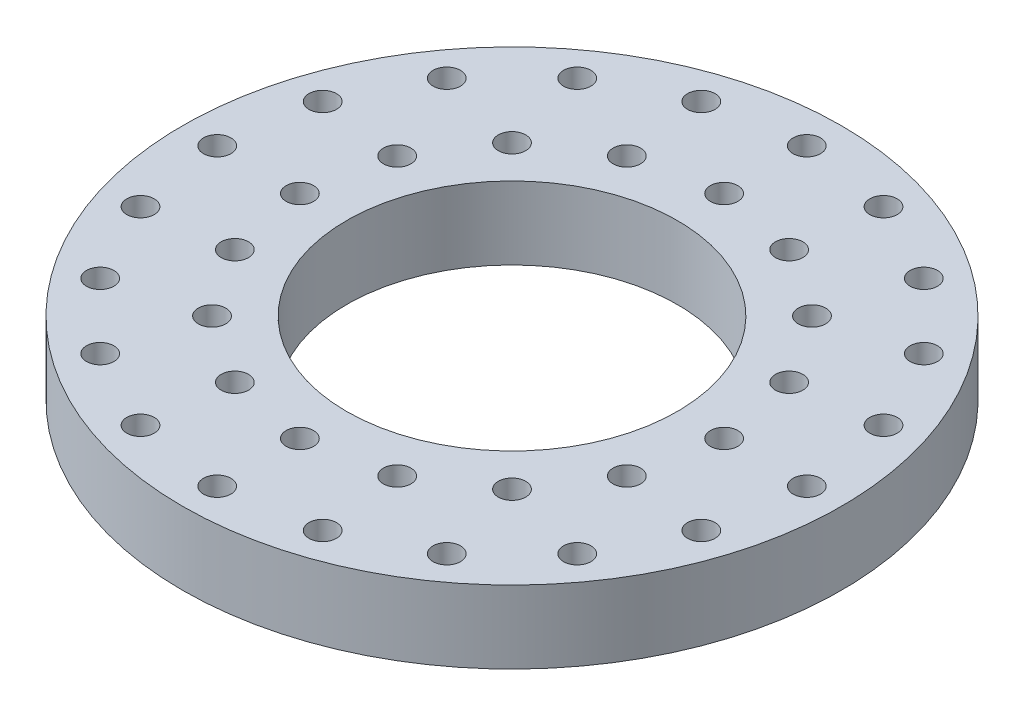
SolidWorks part; units mm, degrees
ref_plane "Front Plane" through (0, 0, 0) normal (0, 0, 1) x (1, 0, 0)
ref_plane "Top Plane" through (0, 0, 0) normal (0, 1, 0) x (1, 0, 0)
ref_plane "Right Plane" through (0, 0, 0) normal (1, 0, 0) x (0, 0, -1)
sketch "Sketch1" plane through (0, 0, 0) normal (0, 1, 0) x (1, 0, 0)
  circle A0 centre (0, 0) radius 101.219
  dimension "D1" = 202.438
extrude "Extrude1" add sketch "Sketch1" along normal blind 22.352
sketch "Sketch2" plane through (0, 0, 0) normal (0, 1, 0) x (1, 0, 0)
  circle A0 centre (0, 0) radius 50.8
extrude "Cut-Extrude1" cut sketch "Sketch2" along normal blind 22.352
sketch "Sketch3" plane through (0, 0, 0) normal (0, 1, 0) x (1, 0, 0)
  circle A0 centre (0, 65.151) radius 4.2164
extrude "Cut-Extrude3" cut sketch "Sketch3" along normal blind 22.352
ref_axis "Axis1" through (0, 103.9235, 0) along (0, -1, 0)
pattern_circular "CirPattern1" count 16 over 360 about axis through (0, 103.9235, 0) along (0, -1, 0) of "Cut-Extrude3"
sketch "Sketch4" plane through (0, 0, 0) normal (0, 1, 0) x (1, 0, 0)
  circle A0 centre (0, 90.551) radius 4.2164
extrude "Cut-Extrude4" cut sketch "Sketch4" along normal blind 22.352
pattern_circular "CirPattern2" count 20 over 360 about axis through (0, 103.9235, 0) along (0, -1, 0) of "Cut-Extrude4"
